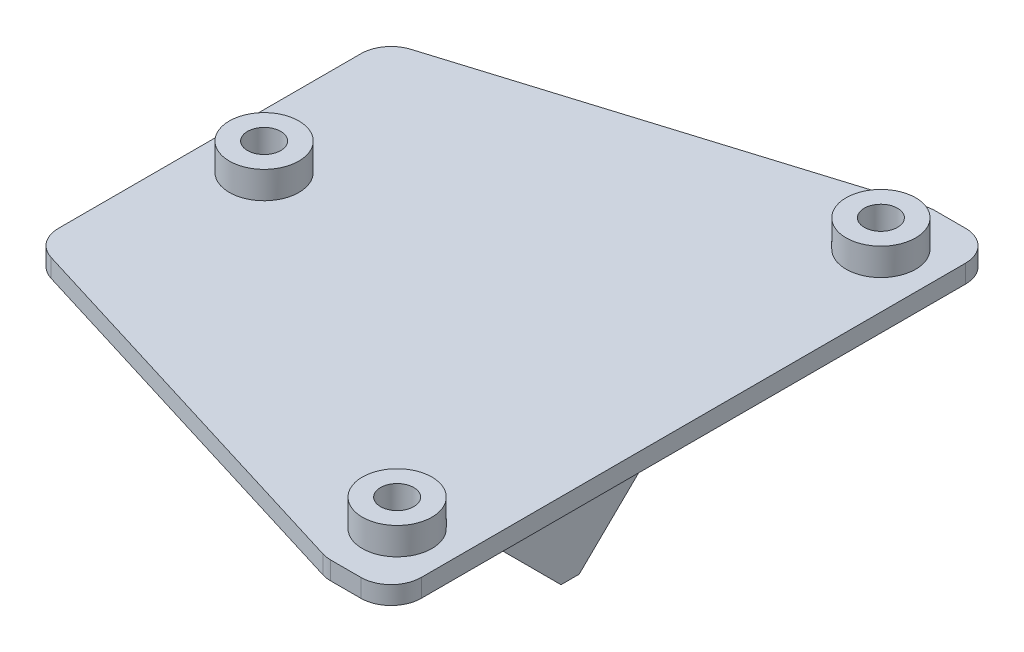
SolidWorks part; units mm, degrees
note: The reader was unsure of these and kept them because the rebuilt part matched: shared geometry of "Sketch3<2>".
ref_plane "Front Plane" through (0, 0, 0) normal (0, 0, 1) x (1, 0, 0)
ref_plane "Top Plane" through (0, 0, 0) normal (0, 1, 0) x (1, 0, 0)
ref_plane "Right Plane" through (0, 0, 0) normal (1, 0, 0) x (0, 0, -1)
sketch "Sketch1" plane through (0, 0, 0) normal (0, 1, 0) x (1, 0, 0)
  line L10 (-35, 50) -> (35, 50)
  line L11 (-40, 45) -> (-40, -45)
  line L12 (-35, -50) -> (35, -50)
  line L13 (40, 45) -> (40, -45)
  line L14 (-40, 50) -> (40, -50) construction
  line L15 (-40, -50) -> (40, 50) construction
  arc A0 (35, 50) -> (40, 45) centre (35, 45) cw
  arc A1 (35, -50) -> (40, -45) centre (35, -45) ccw
  arc A2 (-40, -45) -> (-35, -50) centre (-35, -45) ccw
  arc A3 (-35, 50) -> (-40, 45) centre (-35, 45) ccw
  point P0 (0, 0)
  dimension "D3" = 5
  dimension "D1" = 80
  dimension "D2" = 100
extrude "Boss-Extrude1" add sketch "Sketch1" along normal blind 3
sketch "Sketch2" plane through (0, 3, 0) normal (0, 1, 0) x (1, 0, 0)
  line L0 (-31, 0) -> (0, 0) construction
  line L1 (0, 0) -> (31, 0) construction
  line L2 (31, 40) -> (31, -40) construction
  line L4 (-31, 0) -> (-40, 0) construction
  line L5 (-40, 45) -> (-40, -45) construction
  line L6 (31, 0) -> (40, 0) construction
  line L7 (40, -45) -> (40, 45) construction
  circle A0 centre (-31, 0) radius 2.75
  circle A1 centre (31, 40) radius 2.75
  circle A2 centre (31, -40) radius 2.75
  dimension "D4" = 5.5
  dimension "D1" = 62
  dimension "D3" = 80
extrude "Cut-Extrude1" cut sketch "Sketch2" against normal through all
sketch "Sketch3" plane through (0, 3, 0) normal (0, 1, 0) x (1, 0, 0)
  circle A0 centre (31, -40) radius 2.75 construction
  circle A1 centre (-31, 0) radius 2.75 construction
  circle A2 centre (31, 40) radius 2.75 construction
  circle A3 centre (31, -40) radius 2.75
  circle A4 centre (-31, 0) radius 2.75
  circle A5 centre (31, 40) radius 2.75
  circle A6 centre (-31, 0) radius 5.75
  circle A7 centre (31, 40) radius 5.75
  circle A8 centre (31, -40) radius 5.75
  dimension "D1" = 3
extrude "Boss-Extrude3" add sketch "Sketch3<2>" along normal blind 4.5
sketch "Sketch3<2>" plane through (0, 3, 0) normal (0, 1, 0) x (1, 0, 0) same geometry as "Sketch3"
sketch "Sketch6" plane through (0, 3, 0) normal (0, 1, 0) x (1, 0, 0)
  line L0 (-36.4704, -29.7789) -> (28.5296, -49.7789)
  line L1 (-40, 45) -> (-40, -45) construction
  line L2 (-35, -50) -> (35, -50) construction
  line L3 (-40, 0) -> (40, 0) construction
  line L4 (40, -45) -> (40, 45) construction
  line L5 (-40, -25) -> (-40, -50)
  line L6 (-40, -50) -> (30, -50)
  line L7 (-40, 50) -> (30, 50)
  line L8 (-40, 25) -> (-40, 50)
  line L9 (-36.4704, 29.7789) -> (28.5296, 49.7789)
  arc A1 (-40, -25) -> (-36.4704, -29.7789) centre (-35, -25) ccw
  arc A2 (28.5296, -49.7789) -> (30, -50) centre (30, -45) ccw
  arc A3 (28.5296, 49.7789) -> (30, 50) centre (30, 45) cw
  arc A4 (-40, 25) -> (-36.4704, 29.7789) centre (-35, 25) cw
  point P13 (-6.8506, -26.9469)
  point P16 (23.1468, -50)
  point P18 (27.7776, -50)
  point P19 (0, 0)
  point P26 (0, 0)
  point P27 (-39.3773, -7.4165)
  dimension "D1" = 10
  dimension "D2" = 10
  dimension "D3" = 25
  dimension "D4" = 10
extrude "Cut-Extrude2" cut sketch "Sketch6" against normal blind 4.5
sketch "Sketch7" plane through (0, 0, 0) normal (0, -1, 0) x (1, 0, 0)
  line L0 (-31, 0) -> (-19.6, 0) construction
  line L2 (19.6, 6.7702) -> (19.6, -6.7702)
  line L4 (-19.6, 6.7702) -> (-19.6, -6.7702)
  line L5 (-19.6, 0) -> (19.6, 0) construction
  line L6 (19.6, 0) -> (31, 0) construction
  line L7 (31, 40) -> (31, -40) construction
  line L8 (19.6, 31.5) -> (19.6, 6.7702)
  line L9 (-19.6, -6.7702) -> (-19.6, -31.5)
  line L10 (-19.6, -31.5) -> (-16.6, -31.5)
  line L11 (-16.6, -31.5) -> (-16.6, -1.5)
  line L12 (-16.6, -1.5) -> (16.6, -1.5)
  line L13 (16.6, -1.5) -> (16.6, -31.5)
  line L14 (16.6, -31.5) -> (19.6, -31.5)
  line L15 (19.6, -31.5) -> (19.6, -6.7702)
  line L16 (16.6, 31.5) -> (19.6, 31.5)
  line L17 (16.6, 1.5) -> (16.6, 31.5)
  line L18 (-16.6, 1.5) -> (16.6, 1.5)
  line L19 (-16.6, 31.5) -> (-16.6, 1.5)
  line L20 (-19.6, 31.5) -> (-16.6, 31.5)
  line L21 (-19.6, 6.7702) -> (-19.6, 31.5)
  circle A0 centre (-31, 0) radius 2.75 construction
  point P0 (-0.2885, 14.4741)
  point P15 (-16.2892, -42.4985)
  point P17 (-14.3916, -43.5)
  dimension "D1" = 11.4
  dimension "D2" = 30
  dimension "D3" = 1.5
  dimension "D4" = 3
extrude "Boss-Extrude4" add sketch "Sketch7" along normal blind 30
sketch "Sketch8" plane through (16.6, 0, 0) normal (-1, 0, 0) x (0, 0, 1)
  line L0 (1.5, -30) -> (31.5, 0)
  line L1 (31.5, 0) -> (31.5, -30)
  line L2 (31.5, -30) -> (1.5, -30)
  line L3 (-1.5, -30) -> (-31.5, -30)
  line L4 (-31.5, -30) -> (-31.5, -0.7127)
  line L5 (-31.5, -30) -> (-31.5, 0) construction
  line L6 (-31.5, -0.7127) -> (-1.5, -30)
extrude "Cut-Extrude3" cut sketch "Sketch8" against normal through all both and the other way through all
sketch "Sketch9" plane through (0, 0, -1.5) normal (0, 0, -1) x (-1, 0, 0)
  line L0 (0, 0) -> (0, -30) construction
  line L2 (16.6, -30) -> (-16.6, -30) construction
  line L4 (-8.8388, -23.8388) -> (0, -15) construction
  line L6 (-16.6, -30) -> (-16.6, 0) construction
  line L7 (-16.6, -15) -> (0, -15) construction
  circle A0 centre (0, -15) radius 8
  circle A1 centre (-8.8388, -23.8388) radius 1.75
  circle A2 centre (-8.8388, -6.1612) radius 1.75
  circle A3 centre (8.8388, -23.8388) radius 1.75
  circle A4 centre (8.8388, -6.1612) radius 1.75
  dimension "D1" = 16
  dimension "D2" = 3.5
  dimension "D3" = 12.5
  dimension "D4" = 45
extrude "Cut-Extrude4" cut sketch "Sketch9" against normal through all both
extrude "Boss-Extrude2" add sketch "Sketch3" along normal blind 4.5
sketch "Sketch4" plane through (0, 3, 0) normal (0, 1, 0) x (1, 0, 0)
  line L0 (-55, 0) -> (0, 0) construction
  line L1 (0, 0) -> (45, 0) construction
  circle A0 centre (-55, 0) radius 2.25
  circle A1 centre (45, 0) radius 2.25
  circle A3 centre (-7, 0) radius 2.25
  dimension "D2" = 4.5
  dimension "D1" = 55
  dimension "D3" = 45
  dimension "D4" = 7
